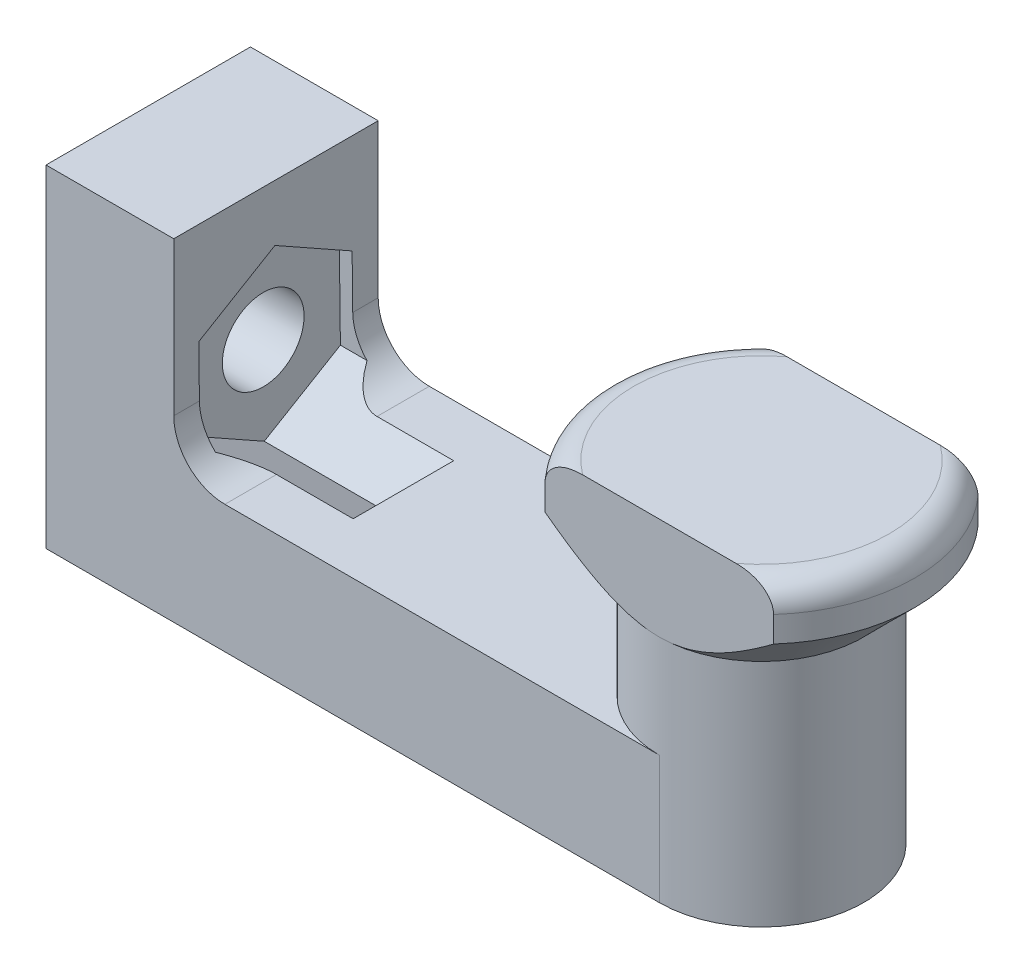
SolidWorks part; units mm, degrees
ref_plane "前视基准面" through (0, 0, 0) normal (0, 0, 1) x (1, 0, 0)
ref_plane "上视基准面" through (0, 0, 0) normal (0, 1, 0) x (1, 0, 0)
ref_plane "右视基准面" through (0, 0, 0) normal (1, 0, 0) x (0, 0, -1)
sketch "草图1" plane through (0, 0, 0) normal (0, 0, 1) x (1, 0, 0)
  line L0 (5, 13) -> (5, 5)
  line L1 (0, 0) -> (28, 0)
  line L2 (0, 0) -> (0, 13)
  line L3 (0, 13) -> (5, 13)
  line L4 (28, 0) -> (28, 9)
  line L5 (5, 5) -> (20, 5)
  line L6 (20, 5) -> (20, 9)
  line L7 (20, 9) -> (28, 9)
  dimension "D1" = 5
  dimension "D2" = 15
  dimension "D3" = 8
  dimension "D4" = 4
  dimension "D5" = 5
  dimension "D6" = 8
extrude "凸台-拉伸1" add sketch "草图1" along normal blind 8
sketch "草图2" plane through (0, 9, 0) normal (0, 1, 0) x (1, 0, 0)
  line L0 (28, 0) -> (20, 0) construction
  line L1 (13.9991, 0.8349) -> (29.3738, 0.8349)
  line L2 (13.9991, 0.8349) -> (13.9991, -9.0062)
  line L3 (13.9991, -9.0062) -> (29.3738, -9.0062)
  line L4 (29.3738, 0.8349) -> (29.3738, -9.0062)
  line L5 (20, -8) -> (20, 0) construction
  line L6 (28, -8) -> (28, 0) construction
  line L7 (28, -8) -> (20, -8) construction
  line L8 (28, 0) -> (20, 0) construction
  line L9 (20, -8) -> (20, 0) construction
  line L10 (28, -8) -> (28, 0) construction
  line L11 (28, -8) -> (20, -8) construction
  circle A0 centre (24, -4) radius 4
extrude "切除-拉伸1" cut sketch "草图2" against normal up to surface (4 mm away) up to face at (12.5, 5, 4)
sketch "草图3" plane through (0, 5, 0) normal (0, 1, 0) x (1, 0, 0)
  line L1 (28, 0) -> (24, 0)
  line L2 (28, 0) -> (28, -8)
  line L3 (28, -8) -> (24, -8)
  line L5 (28, 0) -> (20, 0) construction
  arc A0 (24, -8) -> (24, 0) centre (24, -4) ccw
extrude "切除-拉伸2" cut sketch "草图3" against normal blind 8 contours A0 L2 L1 | A0 L3 L2 region at (27.1065, 5, 0.8935) region at (27.1065, 5, 7.1065)
sketch "草图4" plane through (5, 0, 0) normal (1, 0, 0) x (0, 0, -1)
  line L0 (-4, 13) -> (-4, 0) construction
  line L1 (-8, 13) -> (0, 13) construction
  line L2 (-8, 0) -> (0, 0) construction
  circle A0 centre (-4, 7.3288) radius 1.6
  dimension "D1" = 3.2
extrude "切除-拉伸3" cut sketch "草图4" against normal blind 8
fillet "圆角1" radius 2 1 edges at (5, 5, 4)
sketch "草图7" plane through (5, 0, 0) normal (1, 0, 0) x (0, 0, -1)
  line L1 (-1.0211, 9.0968) -> (-4.0417, 10.7926)
  line L2 (-4.0417, 10.7926) -> (-7.0206, 9.0246)
  line L3 (-7.0206, 9.0246) -> (-6.9789, 5.5607)
  line L4 (-6.9789, 5.5607) -> (-3.9583, 3.8649)
  line L5 (-3.9583, 3.8649) -> (-0.9794, 5.633)
  line L6 (-0.9794, 5.633) -> (-1.0211, 9.0968)
  circle A0 centre (-4, 7.3288) radius 3 construction
  dimension "D1" = 6
extrude "切除-拉伸4" cut sketch "草图7" against normal blind 0.5 and the other way blind 5
ref_plane "基准面1" through (0, 0, 4) normal (0, 0, 1) x (1, 0, 0)
sketch "草图8" plane through (0, 0, 4) normal (0, 0, 1) x (1, 0, 0)
  line L0 (24, 9) -> (24, 11.0807) construction
  line L1 (20, 9) -> (18, 11)
  line L2 (18, 11) -> (18, 13)
  line L3 (18, 13) -> (24, 13)
  line L4 (24, 13) -> (24, 9)
  line L5 (28, 9) -> (20, 9) construction
  line L6 (24, 9) -> (20, 9)
  dimension "D1" = 2
  dimension "D2" = 2
  dimension "D3" = 6
revolve "旋转1" add sketch "草图8" angle 360 about L0
fillet "圆角2" radius 1 1 edges at (24, 13, -2)
sketch "草图9" plane through (0, 13, 0) normal (0, 1, 0) x (1, 0, 0)
  line L1 (18.2187, 3.3247) -> (30.4293, 3.3247)
  line L2 (18.2187, 3.3247) -> (18.2187, 0)
  line L3 (18.2187, 0) -> (30.4293, 0)
  line L4 (30.4293, 3.3247) -> (30.4293, 0)
  line L5 (17.6843, -11.5094) -> (31.6439, -11.5094)
  line L6 (17.6843, -11.5094) -> (17.6843, -8)
  line L7 (17.6843, -8) -> (31.6439, -8)
  line L8 (31.6439, -11.5094) -> (31.6439, -8)
extrude "切除-拉伸5" cut sketch "草图9" against normal blind 10
